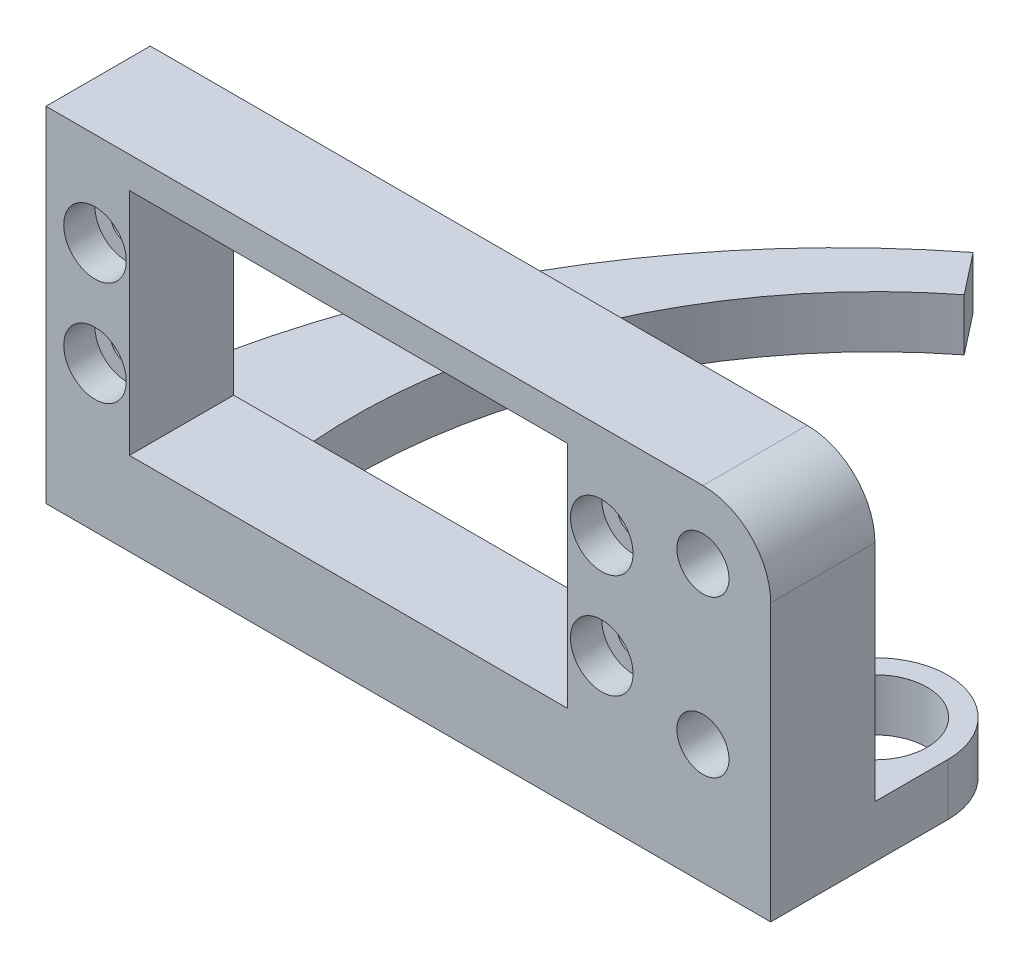
SolidWorks part; units mm, degrees
ref_plane "Front Plane" through (0, 0, 0) normal (0, 0, 1) x (1, 0, 0)
ref_plane "Top Plane" through (0, 0, 0) normal (0, 1, 0) x (1, 0, 0)
ref_plane "Right Plane" through (0, 0, 0) normal (1, 0, 0) x (0, 0, -1)
ref_axis "X" through (-88.99, 0, 0) along (1, 0, 0)
ref_axis "Y" through (0, 55, 0) along (0, -1, 0)
ref_axis "Z" through (0, 0, -88.99) along (0, 0, 1)
sketch "Sketch1" plane through (0, 0, 0) normal (0, 0, 1) x (1, 0, 0)
  line L0 (34, -7.5) -> (34, 7.5) construction
  line L1 (0, 0) -> (34, 0) construction
  line L2 (24.3, 5) -> (24.3, -5) construction
  line L3 (-21, 11) -> (21, 11)
  line L4 (-21, 11) -> (-21, -11)
  line L5 (-21, -11) -> (21, -11)
  line L6 (21, 11) -> (21, -11)
  line L7 (-21, 11) -> (21, -11) construction
  line L8 (-21, -11) -> (21, 11) construction
  line L9 (0, 0) -> (0, 11) construction
  line L10 (34, -14) -> (-29, -14)
  line L11 (-29, -14) -> (-29, 14)
  line L12 (-29, 14) -> (34, 14)
  line L13 (40.5, 7.5) -> (40.5, -7.5)
  line L14 (34, 0) -> (40.5, 0) construction
  line L15 (34, -14) -> (40.5, -14)
  line L16 (40.5, -14) -> (40.5, -7.5)
  circle A0 centre (34, -7.5) radius 2.5
  circle A1 centre (34, 7.5) radius 2.5
  circle A2 centre (24.3, 5) radius 1.5
  circle A3 centre (24.3, -5) radius 1.5
  circle A4 centre (-24.3, -5) radius 1.5
  circle A5 centre (-24.3, 5) radius 1.5
  arc A6 (34, 14) -> (40.5, 7.5) centre (34, 7.5) cw
  arc A7 (40.5, -7.5) -> (34, -14) centre (34, -7.5) cw construction
  point P14 (24.3, 0)
  dimension "D1" = 22
  dimension "D4" = 5
  dimension "D6" = 3
  dimension "D7" = 24.3
  dimension "D10" = 4
  dimension "D2" = 42
  dimension "D3" = 34
  dimension "D5" = 15
  dimension "D8" = 10
  dimension "D9" = 10
  dimension "D11" = 8
extrude "Boss-Extrude1" add sketch "Sketch1" along normal blind 10
sketch "Sketch2" plane through (0, 0, 0) normal (0, 0, 1) x (1, 0, 0)
  circle A0 centre (-24.3, 5) radius 3
  circle A1 centre (-24.3, -5) radius 3
  circle A2 centre (24.3, 5) radius 3
  circle A3 centre (24.3, -5) radius 3
  dimension "D1" = 6
extrude "Cut-Extrude1" cut sketch "Sketch2" against normal blind 3 from surface starting at face at (36.5, 7.5, 10)
sketch "Sketch4" plane through (0, 0, 0) normal (0, 1, 0) x (1, 0, 0)
  line L0 (40.5, 0) -> (40.5, 7)
  line L1 (34, 0) -> (40.5, 0) construction
  line L2 (26.5, 7) -> (26.5, 0)
  line L3 (34, 0) -> (-29, 0) construction
  line L4 (0, 0) -> (34, 0) construction
  line L5 (40.5, 0) -> (26.5, 0)
  line L6 (-29, 0) -> (26.5, 0)
  line L7 (40.5, 0) -> (40.5, -10)
  line L8 (40.5, -10) -> (-29, -10)
  line L9 (-29, -10) -> (-29, 0)
  line L10 (-0.3976, 50.3123) -> (2.684, 46.3748)
  line L11 (-0.3976, 50.3123) -> (3.5399, 53.3939) construction
  arc A0 (40.5, 7) -> (26.5, 7) centre (33.5, 7) ccw
  circle A1 centre (33.5, 7) radius 5
  arc A2 (40.5, 7) -> (26.5, 7) centre (33.5, 7) cw construction
  arc A3 (-16.0076, 0) -> (2.684, 46.3748) centre (33.5, 7) cw
  arc A4 (-0.3976, 50.3123) -> (-29, 0) centre (46.5347, -9.6549) ccw
  dimension "D1" = 10
  dimension "D2" = 2
  dimension "D3" = 50
  dimension "D4" = 5
  dimension "D6" = 5
  dimension "D5" = 60
extrude "Boss-Extrude2" add sketch "Sketch4" against normal blind 5 from surface contours L0 A0 L2 L5 A1 | L9 L8 L7 L5 L6 | L6 A3 L10 region at (33.5, 0, -0.198) region at (5.75, 0, 5) region at (-16.4239, 0, -21.6605) starting at face at (5.75, -14, 5)
